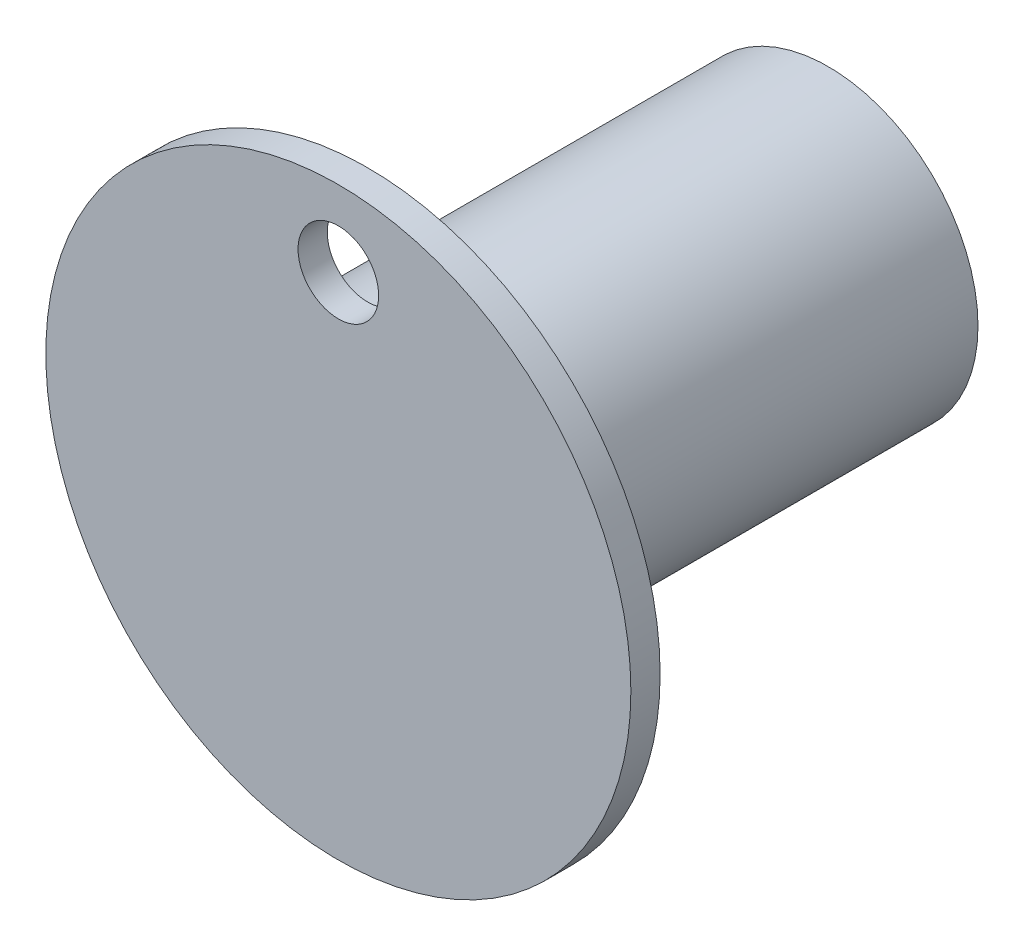
SolidWorks part; units mm, degrees
ref_plane "Front Plane" through (0, 0, 0) normal (0, 0, 1) x (1, 0, 0)
ref_plane "Top Plane" through (0, 0, 0) normal (0, 1, 0) x (1, 0, 0)
ref_plane "Right Plane" through (0, 0, 0) normal (1, 0, 0) x (0, 0, -1)
sketch "Sketch1" plane through (0, 0, 0) normal (0, 0, 1) x (1, 0, 0)
  circle A0 centre (0, 0) radius 6.5
  dimension "D1" = 13
extrude "Boss-Extrude1" add sketch "Sketch1" along normal blind 20
sketch "Sketch2" plane through (0, 0, 20) normal (0, 0, 1) x (1, 0, 0)
  circle A0 centre (0, 0) radius 12.7
  dimension "D1" = 25.4
extrude "Boss-Extrude2" add sketch "Sketch2" along normal blind 1.27
sketch "Sketch3" plane through (0, 0, 0) normal (0, 0, -1) x (-1, 0, 0)
  circle A0 centre (0, 0) radius 1.2
  dimension "D1" = 2.4
extrude "Cut-Extrude1" cut sketch "Sketch3" against normal up to surface (20 mm away) up to face at (6.5, 0, 20)
sketch "Sketch4" plane through (0, 0, 20) normal (0, 0, -1) x (-1, 0, 0)
  circle A0 centre (0, 9.398) radius 1.75
  circle A1 centre (0, 0) radius 12.7 construction
  point P2 (0.3191, 9.3051)
  point P4 (0, 9.3781)
  dimension "D1" = 3.5
  dimension "D2" = 9.398
extrude "Cut-Extrude2" cut sketch "Sketch4" against normal blind 7.62
